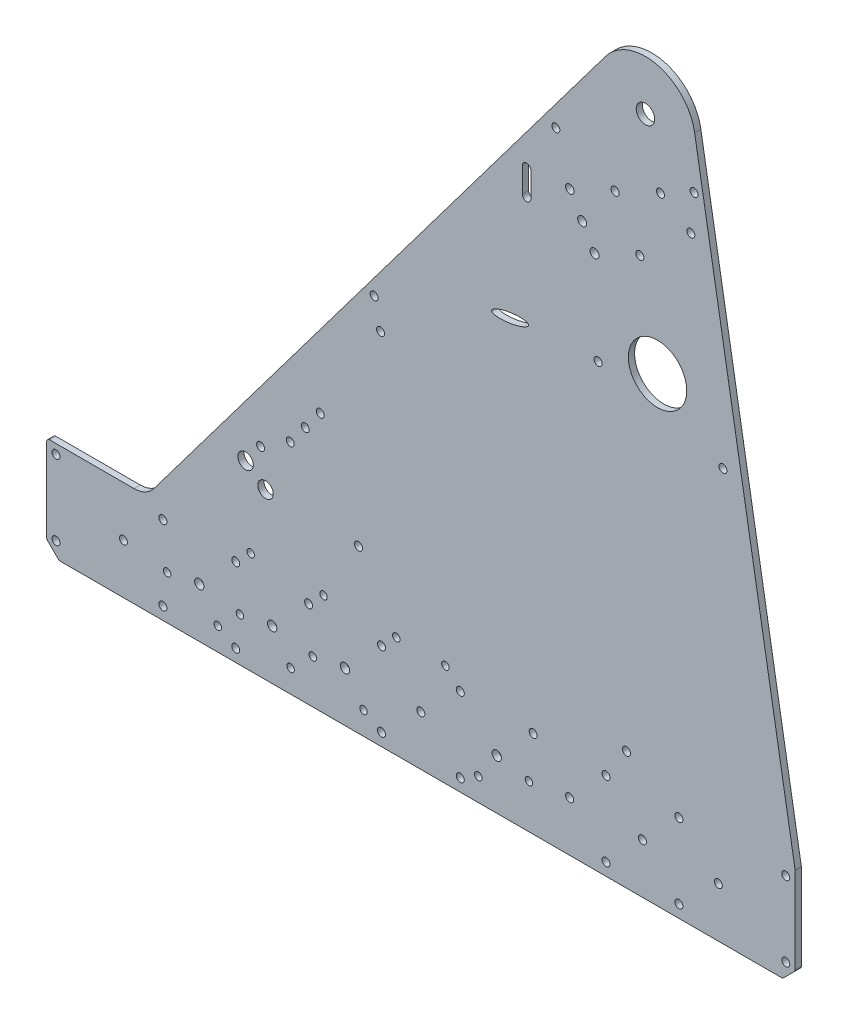
SolidWorks part; units mm, degrees
ref_plane "Front Plane" through (0, 0, 0) normal (0, 0, 1) x (1, 0, 0)
ref_plane "Top Plane" through (0, 0, 0) normal (0, 1, 0) x (1, 0, 0)
ref_plane "Right Plane" through (0, 0, 0) normal (1, 0, 0) x (0, 0, -1)
sketch "Sketch1" plane through (0, 0, 0) normal (0, 0, 1) x (1, 0, 0)
  line L1 (0, 0) -> (381, 0)
  line L2 (0, 0) -> (0, 50.8)
  line L4 (381, 0) -> (381, 50.8)
  line L5 (381, 50.8) -> (329.8374, 350.3513)
  line L6 (0, 50.8) -> (44.463, 50.8)
  line L11 (54.6105, 55.8634) -> (284.5049, 361.3482)
  arc A0 (284.5049, 361.3482) -> (329.8374, 350.3513) centre (304.8, 346.075) cw
  arc A1 (44.463, 50.8) -> (54.6105, 55.8634) centre (44.463, 63.5) ccw
  point P11 (50.8, 50.8)
  dimension "D4" = 346.075
  dimension "D7" = 12.7
  dimension "D5" = 25.4
  dimension "D1" = 50.8
  dimension "D2" = 381
  dimension "D3" = 76.2
  dimension "D6" = 50.8
extrude "Boss-Extrude1" add sketch "Sketch1" along normal blind 3.175
sketch "Sketch2" plane through (0, 0, 3.175) normal (0, 0, 1) x (1, 0, 0)
  line L1 (190.5, 50.8) -> (190.5, 0) construction
  line L3 (0, 0) -> (381, 0) construction
  line L5 (0, 6.35) -> (0, 0)
  line L6 (0, 50.8) -> (0, 0) construction
  line L7 (0, 0) -> (6.35, 0)
  line L8 (6.35, 0) -> (0, 6.35)
  line L9 (381, 0) -> (374.65, 0)
  line L10 (374.65, 0) -> (381, 6.35)
  line L11 (381, 6.35) -> (381, 0)
  circle A19 centre (4.7625, 46.0375) radius 2.032
  circle A20 centre (4.7625, 7.9375) radius 2.032
  circle A21 centre (376.2375, 7.9375) radius 2.032
  circle A22 centre (376.2375, 46.0375) radius 2.032
  dimension "D21" = 6.35
  dimension "D27" = 4.064
  dimension "D4" = 46.0375
  dimension "D22" = 6.35
  dimension "D25" = 4.7625
  dimension "D28" = 7.9375
extrude "Cut-Extrude1" cut sketch "Sketch2" against normal up to next
sketch "Sketch5" plane through (0, 0, 3.175) normal (0, 0, 1) x (1, 0, 0)
  line L0 (151.892, 25.4) -> (229.108, 25.4) construction
  line L1 (229.108, 25.4) -> (341.884, 25.4) construction
  circle A0 centre (39.116, 25.4) radius 2.032
  circle A1 centre (59.182, 6.35) radius 2.032
  circle A2 centre (59.182, 44.45) radius 2.032
  circle A3 centre (96.266, 44.45) radius 2.032
  circle A4 centre (133.35, 44.45) radius 2.032
  circle A5 centre (170.434, 44.45) radius 2.032
  circle A6 centre (210.566, 44.45) radius 2.032
  circle A7 centre (210.566, 6.35) radius 2.032
  circle A8 centre (170.434, 6.35) radius 2.032
  circle A9 centre (247.65, 44.45) radius 2.032
  circle A10 centre (266.192, 25.4) radius 2.032
  circle A11 centre (39.116, 25.4) radius 2.286 construction
  circle A12 centre (59.182, 44.45) radius 1.905 construction
  circle A13 centre (59.182, 6.35) radius 1.905 construction
  circle A14 centre (96.266, 44.45) radius 1.905 construction
  circle A15 centre (133.35, 44.45) radius 1.905 construction
  circle A16 centre (170.434, 44.45) radius 1.905 construction
  circle A17 centre (170.434, 6.35) radius 2.159 construction
  circle A18 centre (210.566, 6.35) radius 2.159 construction
  circle A19 centre (210.566, 44.45) radius 1.905 construction
  circle A20 centre (247.65, 44.45) radius 1.905 construction
  circle A21 centre (266.192, 25.4) radius 2.286 construction
  circle A22 centre (77.724, 25.4) radius 2.3813
  circle A23 centre (114.808, 25.4) radius 2.3813
  circle A24 centre (151.892, 25.4) radius 2.3813
  circle A25 centre (229.108, 25.4) radius 2.3813
  circle A26 centre (190.5, 25.4) radius 2.032
  circle A28 centre (303.276, 25.4) radius 2.032
  circle A29 centre (341.884, 25.4) radius 2.032
  circle A30 centre (77.724, 25.4) radius 7.366 construction
  circle A31 centre (114.808, 25.4) radius 7.366 construction
  circle A32 centre (151.892, 25.4) radius 7.366 construction
  circle A33 centre (229.108, 25.4) radius 7.366 construction
  dimension "D1" = 4.064
  dimension "D2" = 4.7625
  dimension "D3" = 37.084
  dimension "D4" = 38.608
  dimension "D5" = 38.608
extrude "Cut-Extrude4" cut sketch "Sketch5" against normal through all
sketch "Sketch6" plane through (0, 0, 3.175) normal (0, 0, 1) x (1, 0, 0)
  line L0 (6.35, 0) -> (374.65, 0) construction
  line L1 (266.192, 25.4) -> (303.276, 25.4) construction
  line L2 (284.734, 6.35) -> (284.734, 44.45) construction
  line L3 (151.892, 25.4) -> (114.808, 25.4) construction
  line L4 (114.808, 25.4) -> (77.724, 25.4) construction
  circle A0 centre (284.734, 44.45) radius 2.032
  circle A1 centre (284.734, 6.35) radius 2.032
  circle A2 centre (321.818, 6.35) radius 2.032
  circle A3 centre (321.818, 44.45) radius 2.032
  circle A4 centre (96.266, 6.35) radius 2.032
  circle A6 centre (295.148, 60.325) radius 2.032
  circle A7 centre (295.148, 60.325) radius 1.905 construction
  point P8 (284.734, 25.4)
  point P9 (284.734, 25.4)
  point P28 (96.266, 25.4)
  dimension "D1" = 4.064
  dimension "D2" = 6.35
  dimension "D3" = 37.084
extrude "Cut-Extrude5" cut sketch "Sketch6" against normal through all
sketch "Sketch3" plane through (0, 0, 3.175) normal (0, 0, 1) x (1, 0, 0)
  line L1 (381, 6.35) -> (381, 50.8) construction
  line L2 (6.35, 0) -> (374.65, 0) construction
  line L3 (304.8, 346.075) -> (289.3732, 304.3879) construction
  line L4 (266.2957, 293.7771) -> (289.3732, 304.3879) construction
  line L5 (266.2957, 293.7771) -> (272.5866, 282.7446) construction
  line L6 (272.5866, 282.7446) -> (278.8774, 271.7122) construction
  line L7 (381, 50.8) -> (329.8374, 350.3513) construction
  line L8 (244.3127, 279.4) -> (244.3127, 292.1) construction
  line L9 (0, 50.8) -> (0, 6.35) construction
  line L12 (284.5049, 361.3482) -> (54.6105, 55.8634) construction
  line L13 (242.1537, 279.4) -> (242.1537, 292.1)
  line L14 (246.4717, 279.4) -> (246.4717, 292.1)
  line L15 (194.5126, 212.725) -> (217.4224, 243.1676) construction
  line L16 (284.5049, 361.3482) -> (54.6105, 55.8634) construction
  circle A0 centre (304.8, 346.075) radius 4.699
  circle A1 centre (166.6875, 196.85) radius 2.032
  circle A2 centre (158.75, 82.55) radius 2.032
  circle A3 centre (289.3732, 304.3879) radius 2.0955
  circle A5 centre (266.2957, 293.7771) radius 2.159
  circle A6 centre (272.5866, 282.7446) radius 2.286
  circle A7 centre (278.8774, 271.7122) radius 2.286
  circle A8 centre (327.9008, 305.1149) radius 2.032
  circle A9 centre (344.223, 209.55) radius 2.032
  circle A12 centre (259.2118, 317.1783) radius 2.032
  arc A26 (242.1537, 279.4) -> (246.4717, 279.4) centre (244.3127, 279.4) ccw
  arc A27 (246.4717, 292.1) -> (242.1537, 292.1) centre (244.3127, 292.1) ccw
  circle A28 centre (217.4224, 243.1676) radius 2.032
  circle A29 centre (194.5126, 212.725) radius 2.032
  circle A30 centre (329.5323, 323.85) radius 2.032
  circle A35 centre (327.9008, 305.1149) radius 1.905 construction
  circle A36 centre (280.7072, 224.9429) radius 2.032
  circle A37 centre (280.7072, 224.9429) radius 1.905 construction
  point P27 (244.3127, 285.75)
  dimension "D1" = 9.398
  dimension "D3" = 4.064
  dimension "D6" = 4.064
  dimension "D11" = 4.318
  dimension "D10" = 4.191
  dimension "D13" = 4.064
  dimension "D20" = 4.064
  dimension "D18" = 2.159
  dimension "D28" = 17.4625
  dimension "D34" = 4.7625
  dimension "D21" = 38.1
  dimension "D19" = 9.525
  dimension "D29" = 4.064
  dimension "D33" = 4.064
  dimension "D31" = 4.572
  dimension "D4" = 222.25
  dimension "D5" = 82.55
  dimension "D7" = 25.4
  dimension "D8" = 12.7
  dimension "D9" = 44.45
  dimension "D12" = 12.7
  dimension "D14" = 135
  dimension "D15" = 9.525
  dimension "D16" = 85
  dimension "D17" = 209.55
  dimension "D22" = 12.7
  dimension "D23" = 53.975
  dimension "D24" = 6.35
  dimension "D25" = 196.85
  dimension "D26" = 166.6875
  dimension "D27" = 279.4
  dimension "D30" = 30
  dimension "D32" = 212.725
  dimension "D35" = 22.225
extrude "Cut-Extrude2" cut sketch "Sketch3" against normal through all
sketch "Sketch7" plane through (0, 0, 0) normal (0, 0, -1) x (-1, 0, 0)
  line L0 (-284.5049, 361.3482) -> (-54.6105, 55.8634) construction
  line L1 (-1.5875, 50.8) -> (-379.4125, 50.8) construction
  line L2 (-310.959, 234.5808) -> (-226.4577, 220.1482) construction
  line L3 (-381, 50.8) -> (-329.8374, 350.3513) construction
  line L4 (-139.2865, 131.4201) -> (-124.0133, 111.125) construction
  line L5 (-6.35, 0) -> (-374.65, 0) construction
  line L6 (-111.4089, 83.8159) -> (-101.2614, 91.4525) construction
  circle A0 centre (-310.959, 234.5808) radius 14.859
  circle A1 centre (-169.9907, 182.7803) radius 2.032
  circle A2 centre (-108.898, 101.6) radius 2.032
  circle A3 centre (-310.959, 234.5808) radius 15.113 construction
  circle A4 centre (-124.0133, 111.125) radius 2.032
  circle A5 centre (-131.6499, 121.2725) radius 2.032
  circle A6 centre (-139.2865, 131.4201) radius 2.032
  circle A7 centre (-101.2614, 91.4525) radius 3.937
  circle A11 centre (-111.4089, 83.8159) radius 3.937
  circle A14 centre (-312.4507, 314.9987) radius 2.032 construction
  circle A16 centre (-312.4507, 314.9987) radius 2.032
  circle A17 centre (-301.9549, 282.323) radius 2.032
  arc A18 (-299.7324, 282.323) -> (-304.1774, 282.323) centre (-301.9549, 282.323) ccw construction
  ellipse E0 centre (-235.8467, 221.7518) end of major axis (-245.2358, 223.3554) minor radius 2.3813
  point P36 (-131.6499, 121.2725)
  dimension "D1" = 29.718
  dimension "D2" = 4.064
  dimension "D7" = 4.064
  dimension "D11" = 25.4
  dimension "D12" = 4.064
  dimension "D16" = 7.874
  dimension "D3" = 15.875
  dimension "D4" = 15.875
  dimension "D5" = 101.6
  dimension "D6" = 50.8
  dimension "D8" = 4.7625
  dimension "D9" = 19.05
  dimension "D10" = 76.2
  dimension "D13" = 22.225
  dimension "D14" = 111.125
  dimension "D15" = 12.7
  dimension "D17" = 15.875
  dimension "D18" = 12.7
extrude "Cut-Extrude6" cut sketch "Sketch7" against normal through all
fillet "Fillet1" radius 1.5875 6 edges at (374.65, 0, 1.5875) (381, 6.35, 1.5875) (381, 50.8, 1.5875) (6.35, 0, 1.5875) (0, 6.35, 1.5875) (0, 50.8, 1.5875)
sketch "Sketch4" plane through (0, 0, 0) normal (0, 0, -1) x (-1, 0, 0)
  circle A0 centre (-61.3181, 22.2981) radius 1.905 construction
  circle A1 centre (-87.1313, 11.606) radius 1.905 construction
  circle A2 centre (-98.4021, 22.2981) radius 1.905 construction
  circle A3 centre (-124.2153, 11.606) radius 1.905 construction
  circle A4 centre (-135.4861, 22.2981) radius 1.905 construction
  circle A5 centre (-161.2993, 11.606) radius 1.905 construction
  circle A6 centre (-245.5139, 22.2981) radius 1.905 construction
  circle A7 centre (-219.7007, 11.606) radius 1.905 construction
  circle A8 centre (-202.982, 51.9684) radius 1.905 construction
  circle A9 centre (-178.018, 51.9684) radius 1.905 construction
  circle A10 centre (-140.934, 51.9684) radius 1.905 construction
  circle A11 centre (-103.85, 51.9684) radius 1.905 construction
  circle A12 centre (-61.3181, 22.2981) radius 1.905
  circle A13 centre (-87.1313, 11.606) radius 1.905
  circle A14 centre (-98.4021, 22.2981) radius 1.905
  circle A15 centre (-124.2153, 11.606) radius 1.905
  circle A16 centre (-135.4861, 22.2981) radius 1.905
  circle A17 centre (-161.2993, 11.606) radius 1.905
  circle A18 centre (-245.5139, 22.2981) radius 1.905
  circle A19 centre (-219.7007, 11.606) radius 1.905
  circle A20 centre (-202.982, 51.9684) radius 1.905
  circle A21 centre (-178.018, 51.9684) radius 1.905
  circle A22 centre (-140.934, 51.9684) radius 1.905
  circle A23 centre (-103.85, 51.9684) radius 1.905
extrude "Cut-Extrude3" cut sketch "Sketch4" against normal up to next
sketch "Sketch8" [suppressed] plane through (0, 0, 0) normal (0, 0, -1) x (-1, 0, 0)
  circle A0 centre (-139.2865, 131.4201) radius 2.032 construction
  circle A1 centre (-131.6499, 121.2725) radius 2.032 construction
  circle A2 centre (-124.0133, 111.125) radius 2.032 construction
  circle A3 centre (-301.9549, 282.323) radius 2.032 construction
  circle A4 centre (-312.4507, 314.9987) radius 2.032 construction
  circle A5 centre (-139.2865, 131.4201) radius 2.032
  circle A6 centre (-131.6499, 121.2725) radius 2.032
  circle A7 centre (-124.0133, 111.125) radius 2.032
  circle A8 centre (-301.9549, 282.323) radius 2.032
  circle A9 centre (-312.4507, 314.9987) radius 2.032
  circle A10 centre (-111.4089, 83.8159) radius 3.937 construction
  circle A11 centre (-101.2614, 91.4525) radius 3.937 construction
  circle A12 centre (-111.4089, 83.8159) radius 3.937
  circle A13 centre (-101.2614, 91.4525) radius 3.937
  ellipse E0 centre (-235.8467, 221.7518) end of major axis (-245.2358, 223.3554) minor radius 2.3813 construction
  ellipse E1 centre (-235.8467, 221.7518) end of major axis (-245.2358, 223.3554) minor radius 2.3813
extrude "Boss-Extrude2" [suppressed] add sketch "Sketch8" against normal up to surface (3.175 mm away) up to face at (63.2231, 22.2981, 3.175)
sketch "Sketch9" plane through (0, 0, 0) normal (0, 0, -1) x (-1, 0, 0)
  circle A0 centre (-194.5126, 212.725) radius 2.032 construction
  circle A1 centre (-217.4224, 243.1676) radius 2.032 construction
  circle A2 centre (-194.5126, 212.725) radius 2.032
  circle A3 centre (-217.4224, 243.1676) radius 2.032
extrude "Boss-Extrude3" add sketch "Sketch9" against normal up to surface (3.175 mm away) up to face at (63.2231, 22.2981, 3.175)
